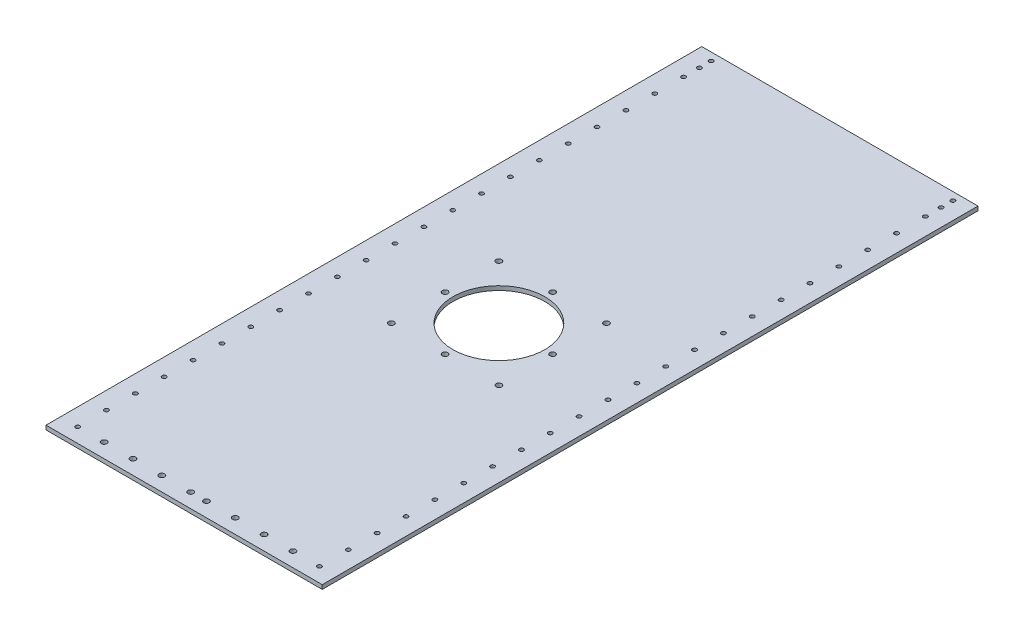
SolidWorks part; units mm, degrees
ref_plane "Front Plane" through (0, 0, 0) normal (0, 0, 1) x (1, 0, 0)
ref_plane "Top Plane" through (0, 0, 0) normal (0, 1, 0) x (1, 0, 0)
ref_plane "Right Plane" through (0, 0, 0) normal (1, 0, 0) x (0, 0, -1)
sketch "Sketch1" plane through (0, 0, 0) normal (0, 1, 0) x (1, 0, 0)
  line L0 (0, 250) -> (0, -250) construction
  line L1 (-105.305, -250) -> (105.305, -250)
  line L2 (-105.305, -250) -> (-105.305, 250)
  line L3 (-105.305, 250) -> (105.305, 250)
  line L4 (105.305, -250) -> (105.305, 250)
  line L5 (-105.305, -250) -> (105.305, 250) construction
  line L6 (-105.305, 250) -> (105.305, -250) construction
  line L7 (-105.305, -10) -> (105.305, -10) construction
  circle A0 centre (92.18, 244) radius 1.6
  circle A1 centre (92.18, 235) radius 1.6
  circle A2 centre (92.18, 223) radius 1.6
  circle A3 centre (92.18, 201) radius 1.6
  circle A4 centre (92.18, 179) radius 1.6
  circle A5 centre (92.18, 157) radius 1.6
  circle A6 centre (92.18, 135) radius 1.6
  circle A7 centre (92.18, 113) radius 1.6
  circle A8 centre (92.18, 91) radius 1.6
  circle A9 centre (92.18, 69) radius 1.6
  circle A10 centre (92.18, 47) radius 1.6
  circle A11 centre (92.18, 25) radius 1.6
  circle A12 centre (92.18, 3) radius 1.6
  circle A13 centre (92.18, -19) radius 1.6
  circle A14 centre (92.18, -41) radius 1.6
  circle A15 centre (92.18, -63) radius 1.6
  circle A16 centre (92.18, -85) radius 1.6
  circle A17 centre (92.18, -107) radius 1.6
  circle A18 centre (92.18, -129) radius 1.6
  circle A19 centre (92.18, -151) radius 1.6
  circle A20 centre (92.18, -173) radius 1.6
  circle A21 centre (92.18, -195) radius 1.6
  circle A22 centre (92.18, -217) radius 1.6
  circle A23 centre (92.18, -239) radius 1.6
  circle A24 centre (-92.18, 69) radius 1.6
  circle A25 centre (-92.18, 91) radius 1.6
  circle A26 centre (-92.18, 113) radius 1.6
  circle A27 centre (-92.18, 135) radius 1.6
  circle A28 centre (-92.18, 157) radius 1.6
  circle A29 centre (-92.18, 179) radius 1.6
  circle A30 centre (-92.18, 201) radius 1.6
  circle A31 centre (-92.18, 223) radius 1.6
  circle A32 centre (-92.18, 235) radius 1.6
  circle A33 centre (-92.18, -239) radius 1.6
  circle A34 centre (-92.18, -217) radius 1.6
  circle A35 centre (-92.18, -195) radius 1.6
  circle A36 centre (-92.18, -173) radius 1.6
  circle A37 centre (-92.18, -151) radius 1.6
  circle A38 centre (-92.18, -129) radius 1.6
  circle A39 centre (-92.18, -107) radius 1.6
  circle A40 centre (-92.18, -85) radius 1.6
  circle A41 centre (-92.18, -63) radius 1.6
  circle A42 centre (-92.18, -41) radius 1.6
  circle A43 centre (-92.18, -19) radius 1.6
  circle A44 centre (-92.18, 3) radius 1.6
  circle A45 centre (-92.18, 25) radius 1.6
  circle A46 centre (-92.18, 47) radius 1.6
  circle A47 centre (-92.18, 244) radius 1.6
  circle A48 centre (6, -239) radius 2.125
  circle A49 centre (28, -239) radius 2.125
  circle A50 centre (50, -239) radius 2.125
  circle A51 centre (72, -239) radius 2.125
  circle A220 centre (-72, -239) radius 2.125
  circle A221 centre (-50, -239) radius 2.125
  circle A222 centre (-28, -239) radius 2.125
  circle A223 centre (-6, -239) radius 2.125
  circle A224 centre (28, -217) radius 2.125 [skipped]
  circle A225 centre (50, -217) radius 2.125 [skipped]
  circle A226 centre (28, -195) radius 2.125 [skipped]
  circle A227 centre (50, -195) radius 2.125 [skipped]
  circle A228 centre (28, -173) radius 2.125 [skipped]
  circle A229 centre (50, -173) radius 2.125 [skipped]
  circle A230 centre (28, -151) radius 2.125 [skipped]
  circle A231 centre (50, -151) radius 2.125 [skipped]
  circle A232 centre (28, -129) radius 2.125 [skipped]
  circle A233 centre (50, -129) radius 2.125 [skipped]
  circle A234 centre (28, -107) radius 2.125 [skipped]
  circle A235 centre (50, -107) radius 2.125 [skipped]
  circle A236 centre (28, -85) radius 2.125 [skipped]
  circle A237 centre (50, -85) radius 2.125 [skipped]
  circle A238 centre (28, -63) radius 2.125 [skipped]
  circle A239 centre (50, -63) radius 2.125 [skipped]
  circle A240 centre (28, -41) radius 2.125 [skipped]
  circle A241 centre (50, -41) radius 2.125 [skipped]
  circle A242 centre (28, -19) radius 2.125 [skipped]
  circle A243 centre (50, -19) radius 2.125 [skipped]
  circle A244 centre (28, 3) radius 2.125 [skipped]
  circle A245 centre (50, 3) radius 2.125 [skipped]
  circle A246 centre (28, 25) radius 2.125 [skipped]
  circle A247 centre (50, 25) radius 2.125 [skipped]
  circle A248 centre (28, 47) radius 2.125 [skipped]
  circle A249 centre (50, 47) radius 2.125 [skipped]
  circle A250 centre (28, 69) radius 2.125 [skipped]
  circle A251 centre (50, 69) radius 2.125 [skipped]
  circle A252 centre (28, 91) radius 2.125 [skipped]
  circle A253 centre (50, 91) radius 2.125 [skipped]
  circle A254 centre (28, 113) radius 2.125 [skipped]
  circle A255 centre (50, 113) radius 2.125 [skipped]
  circle A256 centre (28, 135) radius 2.125 [skipped]
  circle A257 centre (50, 135) radius 2.125 [skipped]
  circle A258 centre (28, 157) radius 2.125 [skipped]
  circle A259 centre (50, 157) radius 2.125 [skipped]
  circle A260 centre (28, 179) radius 2.125 [skipped]
  circle A261 centre (50, 179) radius 2.125 [skipped]
  circle A262 centre (28, 201) radius 2.125 [skipped]
  circle A263 centre (50, 201) radius 2.125 [skipped]
  circle A264 centre (28, 223) radius 2.125 [skipped]
  circle A265 centre (50, 223) radius 2.125 [skipped]
  circle A266 centre (6, -217) radius 2.125 [skipped]
  circle A267 centre (6, -195) radius 2.125 [skipped]
  circle A268 centre (6, -173) radius 2.125 [skipped]
  circle A269 centre (6, -151) radius 2.125 [skipped]
  circle A270 centre (6, -129) radius 2.125 [skipped]
  circle A271 centre (6, -107) radius 2.125 [skipped]
  circle A272 centre (6, -85) radius 2.125 [skipped]
  circle A273 centre (6, -63) radius 2.125 [skipped]
  circle A274 centre (6, -41) radius 2.125 [skipped]
  circle A275 centre (6, -19) radius 2.125 [skipped]
  circle A276 centre (6, 3) radius 2.125 [skipped]
  circle A277 centre (6, 25) radius 2.125 [skipped]
  circle A278 centre (6, 47) radius 2.125 [skipped]
  circle A279 centre (6, 69) radius 2.125 [skipped]
  circle A280 centre (6, 91) radius 2.125 [skipped]
  circle A281 centre (6, 113) radius 2.125 [skipped]
  circle A282 centre (6, 135) radius 2.125 [skipped]
  circle A283 centre (6, 157) radius 2.125 [skipped]
  circle A284 centre (6, 179) radius 2.125 [skipped]
  circle A285 centre (6, 201) radius 2.125 [skipped]
  circle A286 centre (6, 223) radius 2.125 [skipped]
  circle A287 centre (72, -217) radius 2.125 [skipped]
  circle A288 centre (72, -195) radius 2.125 [skipped]
  circle A289 centre (72, -173) radius 2.125 [skipped]
  circle A290 centre (72, -151) radius 2.125 [skipped]
  circle A291 centre (72, -129) radius 2.125 [skipped]
  circle A292 centre (72, -107) radius 2.125 [skipped]
  circle A293 centre (72, -85) radius 2.125 [skipped]
  circle A294 centre (72, -63) radius 2.125 [skipped]
  circle A295 centre (72, -41) radius 2.125 [skipped]
  circle A296 centre (72, -19) radius 2.125 [skipped]
  circle A297 centre (72, 3) radius 2.125 [skipped]
  circle A298 centre (72, 25) radius 2.125 [skipped]
  circle A299 centre (72, 47) radius 2.125 [skipped]
  circle A300 centre (72, 69) radius 2.125 [skipped]
  circle A301 centre (72, 91) radius 2.125 [skipped]
  circle A302 centre (72, 113) radius 2.125 [skipped]
  circle A303 centre (72, 135) radius 2.125 [skipped]
  circle A304 centre (72, 157) radius 2.125 [skipped]
  circle A305 centre (72, 179) radius 2.125 [skipped]
  circle A306 centre (72, 201) radius 2.125 [skipped]
  circle A307 centre (72, 223) radius 2.125 [skipped]
  circle A310 centre (0, -10) radius 35
  circle A311 centre (41, -10) radius 2.125
  circle A312 centre (0, 31) radius 2.125
  circle A313 centre (41, 31) radius 2.125
  circle A314 centre (-41, -10) radius 2.125
  circle A315 centre (-41, 31) radius 2.125
  circle A316 centre (41, -51) radius 2.125
  circle A317 centre (0, -51) radius 2.125
  circle A318 centre (-41, -51) radius 2.125
  dimension "D3" = 3.2
  dimension "D8" = 3.2
  dimension "D9" = 3.2
  dimension "D11" = 4.25
  dimension "D16" = 70
  dimension "D17" = 4.25
  dimension "D19" = 4.25
  dimension "D21" = 4.25
  dimension "D2" = 500
  dimension "D4" = 13.125
  dimension "D5" = 6
  dimension "D6" = 9
  dimension "D7" = 12
  dimension "D12" = 6
  dimension "D15" = 240
  dimension "D18" = 41
  dimension "D20" = 41
  dimension "D22" = 41
  dimension "D23" = 41
  dimension "D10" = 22
  dimension "D13" = 4
  dimension "D14" = 22
extrude "Boss-Extrude1" add sketch "Sketch1" along normal blind 3.175
equation "\"m3\"=3.2"
equation "\"D3@Sketch1\"=\"m3\""
equation "\"D8@Sketch1\"=\"m3\""
equation "\"D9@Sketch1\"=\"m3\""
